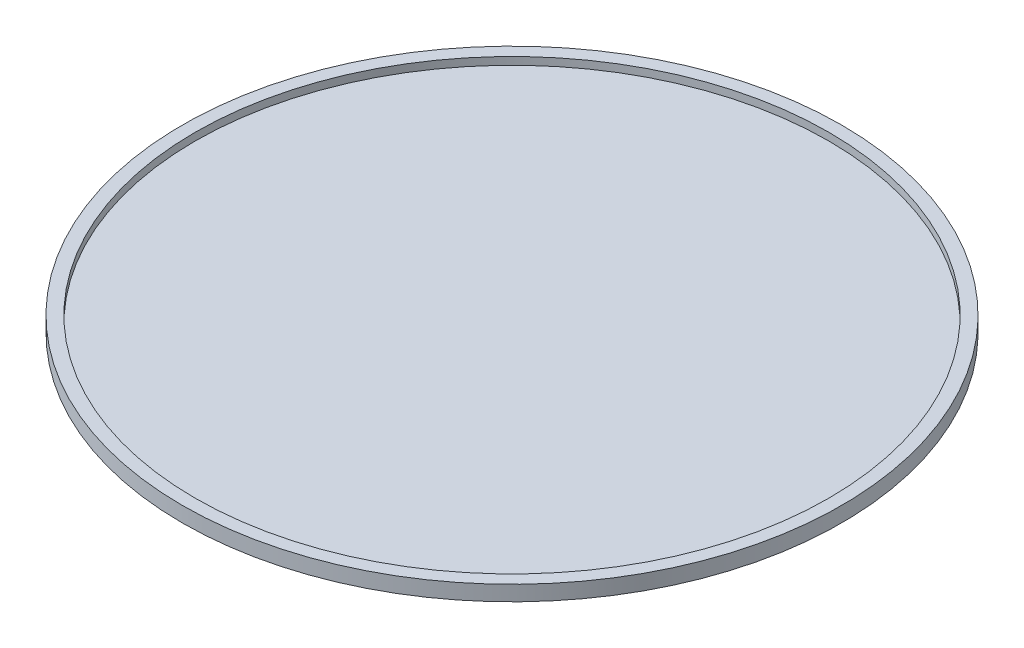
SolidWorks part; units mm, degrees
ref_plane "Front Plane" through (0, 0, 0) normal (0, 0, 1) x (1, 0, 0)
ref_plane "Top Plane" through (0, 0, 0) normal (0, 1, 0) x (1, 0, 0)
ref_plane "Right Plane" through (0, 0, 0) normal (1, 0, 0) x (0, 0, -1)
sketch "Sketch1" plane through (0, 0, 0) normal (0, 1, 0) x (1, 0, 0)
  circle A0 centre (0, 0) radius 125
extrude "Boss-Extrude1" add sketch "Sketch1" along normal blind 3
sketch "Sketch2" plane through (0, 3, 0) normal (0, 1, 0) x (1, 0, 0)
  circle A0 centre (0, 0) radius 130
  circle A1 centre (0, 0) radius 125
extrude "Boss-Extrude2" add sketch "Sketch2" along normal blind 3 and the other way up to surface (3 mm away) other way up to face at (0, 0, 125)
sketch "Sketch3" plane through (0, 0, 0) normal (0, -1, 0) x (1, 0, 0)
  line L0 (0, 2.6811) -> (130, 0)
  line L1 (0, 2.6811) -> (0, -130)
  circle A0 centre (0, 0) radius 130 construction
